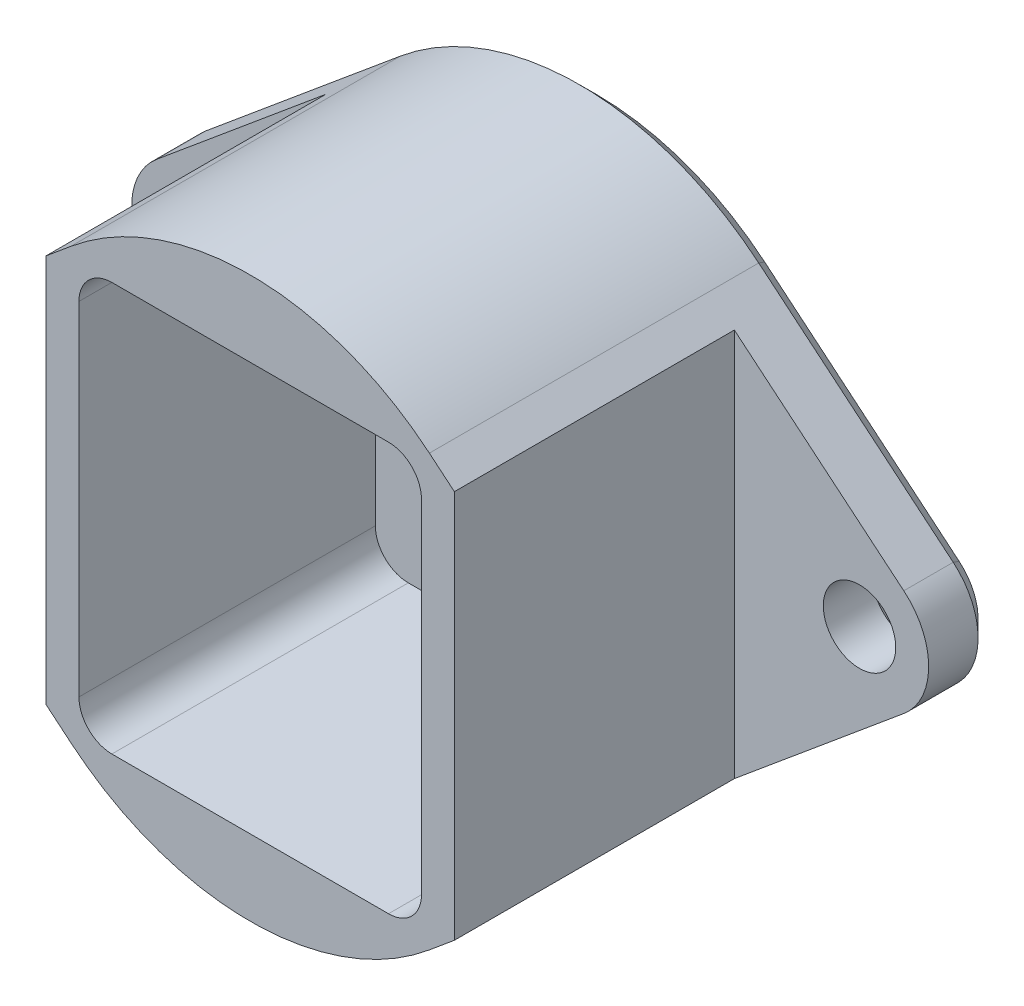
SolidWorks part; units mm, degrees
material "ABS"
ref_plane "Front" through (0, 0, 0) normal (0, 0, 1) x (1, 0, 0)
ref_plane "Top" through (0, 0, 0) normal (0, 1, 0) x (1, 0, 0)
ref_plane "Right" through (0, 0, 0) normal (1, 0, 0) x (0, 0, -1)
sketch "Эскиз2" plane through (0, 0, 0) normal (0, 0, 1) x (1, 0, 0)
  line L0 (5.44, 6.5312) -> (11.344, 1.6136)
  line L1 (11.344, -1.6136) -> (5.44, -6.5312)
  line L2 (-10, 0) -> (10, 0) construction
  line L3 (-5.44, -6.5312) -> (-11.344, -1.6136)
  line L4 (-5.44, 6.5312) -> (-11.344, 1.6136)
  line L5 (0, -8.5) -> (0, 8.5) construction
  arc A1 (11.344, 1.6136) -> (11.344, -1.6136) centre (10, 0) cw
  circle A2 centre (10, 0) radius 1.1
  arc A3 (5.44, -6.5312) -> (-5.44, -6.5312) centre (0, 0) cw
  circle A4 centre (-10, 0) radius 1.1
  arc A5 (-11.344, -1.6136) -> (-11.344, 1.6136) centre (-10, 0) cw
  arc A6 (5.44, 6.5312) -> (-5.44, 6.5312) centre (0, 0) ccw
  circle A7 centre (0, 4.5) radius 1
  circle A9 centre (0, -4.5) radius 1
  circle A10 centre (0, 0) radius 1.7
  point P12 (0, 0)
  dimension "D1" = 2.2
  dimension "D2" = 2.1
  dimension "D4" = 17
  dimension "D5" = 2
  dimension "D7" = 3.4
  dimension "D3" = 20
  dimension "D6" = 9
extrude "Основание" add sketch "Эскиз2" along normal blind 2
sketch "Эскиз3" plane through (0, 0, 2) normal (0, 0, 1) x (1, 0, 0)
  line L0 (11.344, 1.6136) -> (5.44, 6.5312) construction
  line L1 (6.2, 5.8982) -> (6.2, -5.8982)
  line L2 (4.2, 6.2) -> (-4.2, 6.2)
  line L3 (5.2, 5.2) -> (5.2, -5.2)
  line L4 (4.2, -6.2) -> (-4.2, -6.2)
  line L5 (-5.2, 5.2) -> (-5.2, -5.2)
  line L6 (5.2, 6.2) -> (-5.2, -6.2) construction
  line L7 (5.2, -6.2) -> (-5.2, 6.2) construction
  line L8 (-6.2, -5.8982) -> (-6.2, 5.8982)
  line L9 (-11.344, -1.6136) -> (-5.44, -6.5312) construction
  line L10 (5.44, -6.5312) -> (11.344, -1.6136) construction
  line L11 (6.2, -5.8982) -> (5.44, -6.5312)
  line L12 (-6.2, -5.8982) -> (-5.44, -6.5312)
  line L13 (-5.44, 6.5312) -> (-11.344, 1.6136) construction
  line L14 (-6.2, 5.8982) -> (-5.44, 6.5312)
  line L15 (6.2, 5.8982) -> (5.44, 6.5312)
  arc A1 (-4.2, -6.2) -> (-5.2, -5.2) centre (-4.2, -5.2) cw
  arc A6 (4.2, -6.2) -> (5.2, -5.2) centre (4.2, -5.2) ccw
  arc A7 (5.2, 5.2) -> (4.2, 6.2) centre (4.2, 5.2) ccw
  arc A8 (-4.2, 6.2) -> (-5.2, 5.2) centre (-4.2, 5.2) ccw
  arc A9 (5.44, 6.5312) -> (-5.44, 6.5312) centre (0, 0) ccw
  circle A10 centre (0, 0) radius 7.6843 construction
  arc A11 (-5.44, -6.5312) -> (5.44, -6.5312) centre (0, 0) ccw
  arc A12 (-5.44, -6.5312) -> (5.44, -6.5312) centre (0, 0) ccw construction
  arc A13 (5.44, 6.5312) -> (-5.44, 6.5312) centre (0, 0) ccw construction
  dimension "D1" = 12.4
  dimension "D3" = 1
  dimension "D4" = 1
  dimension "D2" = 10.4
extrude "Стенки" add sketch "Эскиз3" along normal offset from surface (8.5 mm away) 10.5 up to face at (0, 0, 0)
sketch "Эскиз4" plane through (0, 0, 2) normal (0, 0, 1) x (1, 0, 0)
  line L0 (5.2, -5.2) -> (5.2, 5.2) construction
  line L1 (-4.2, -6.2) -> (4.2, -6.2)
  line L2 (-5.2, -5.2) -> (-5.2, 5.2)
  line L3 (-4.2, 6.2) -> (4.2, 6.2)
  line L4 (5.2, -5.2) -> (5.2, 5.2)
  line L5 (-5.2, -6.2) -> (5.2, 6.2) construction
  line L6 (-5.2, 6.2) -> (5.2, -6.2) construction
  arc A0 (4.2, -6.2) -> (5.2, -5.2) centre (4.2, -5.2) ccw
  arc A1 (4.2, 6.2) -> (5.2, 5.2) centre (4.2, 5.2) cw
  arc A2 (-4.2, 6.2) -> (-5.2, 5.2) centre (-4.2, 5.2) ccw
  arc A3 (-5.2, -5.2) -> (-4.2, -6.2) centre (-4.2, -5.2) ccw
  arc A4 (4.2, -6.2) -> (5.2, -5.2) centre (4.2, -5.2) ccw construction
  point P0 (0, 0)
extrude "Вырез дополнительный" cut sketch "Эскиз4" against normal blind 0.5
sketch "Эскиз5" plane through (0, 0, 1.5) normal (0, 0, 1) x (1, 0, 0)
  circle A0 centre (0, 0) radius 2.25
  dimension "D1" = 4.5
extrude "Вырез под ободок вала" cut sketch "Эскиз5" against normal blind 0.9
chamfer "Фаска под винты М1.6" distance 0.8 angle 45 2 edges at (-1, -4.5, 0) (1, 4.5, 0)
chamfer "Фаска1" distance 0.5 angle 45 11 edges at (-8.9, 0, 0) (1.7, 0, 0) (11.1, 0, 0) (-8.392, 4.0724, 0) (-12.1, 0, 0) (-8.392, -4.0724, 0) (8.392, -4.0724, 0) (12.1, 0, 0) (8.392, 4.0724, 0) (0, -8.5, 0) (0, 8.5, 0)
